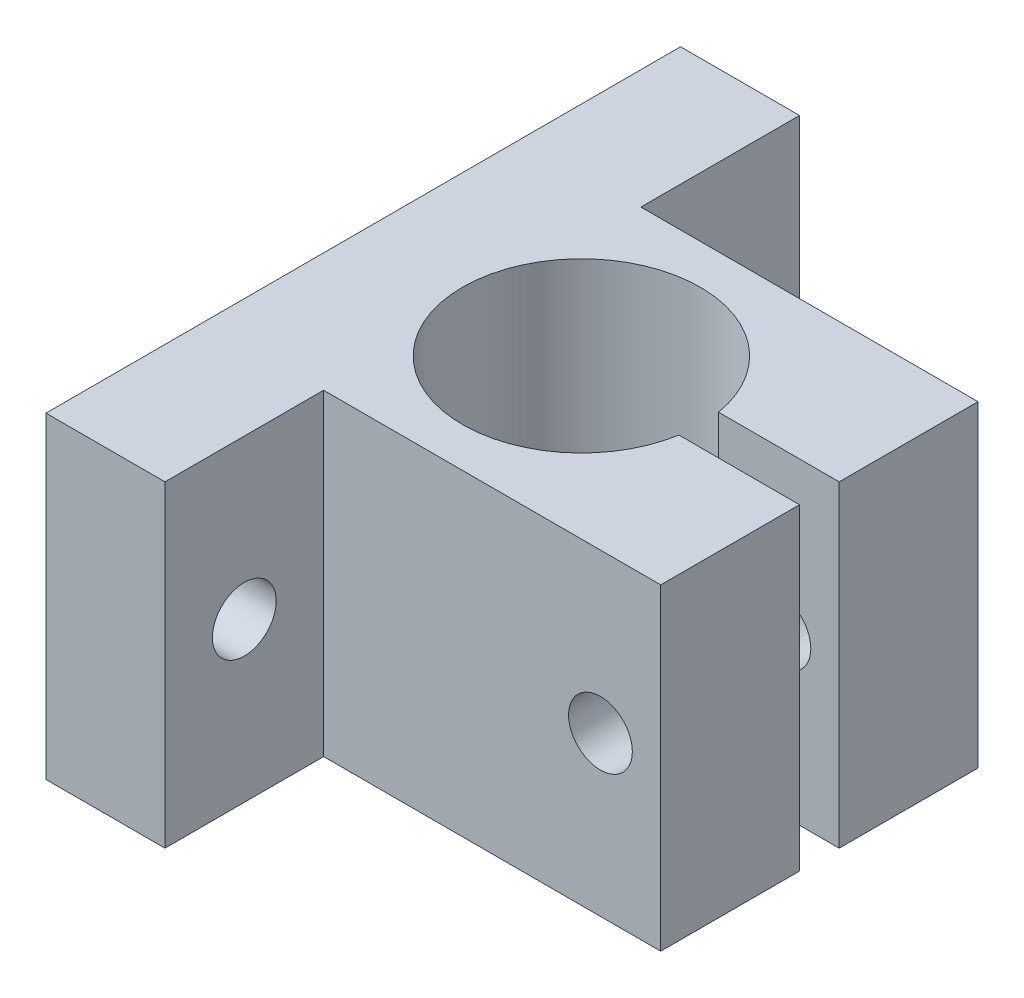
SolidWorks part; units mm, degrees
material "6061 Alloy"
ref_plane "Front Plane" through (0, 0, 0) normal (0, 0, 1) x (1, 0, 0)
ref_plane "Top Plane" through (0, 0, 0) normal (0, 1, 0) x (1, 0, 0)
ref_plane "Right Plane" through (0, 0, 0) normal (1, 0, 0) x (0, 0, -1)
sketch "Sketch1" plane through (0, 0, 0) normal (0, 1, 0) x (1, 0, 0)
  line L1 (-25.4, 25.4) -> (25.4, 25.4)
  line L2 (-25.4, 25.4) -> (-25.4, -25.4)
  line L3 (-25.4, -25.4) -> (25.4, -25.4)
  line L4 (25.4, 25.4) -> (25.4, -25.4)
  line L5 (-25.4, 25.4) -> (25.4, -25.4) construction
  line L6 (-25.4, -25.4) -> (25.4, 25.4) construction
  point P0 (0, 0)
  dimension "D1" = 50.8
  dimension "D2" = 50.8
extrude "Boss-Extrude1" add sketch "Sketch1" along normal mid plane 25.4
sketch "Sketch2" plane through (0, 12.7, 0) normal (0, 1, 0) x (1, 0, 0)
  line L0 (-25.4, 25.4) -> (-25.4, -25.4) construction
  circle A0 centre (-7.9375, 0) radius 9.525
  dimension "D1" = 19.05
  dimension "D2" = 17.4625
extrude "Cut-Extrude1" cut sketch "Sketch2" against normal through all
sketch "Sketch11" plane through (0, 12.7, 0) normal (0, 1, 0) x (1, 0, 0)
  line L0 (25.4, 25.4) -> (-25.4, 25.4) construction
  line L1 (11.1125, 25.4) -> (25.4, 25.4)
  line L2 (11.1125, 25.4) -> (11.1125, -25.4)
  line L3 (11.1125, -25.4) -> (25.4, -25.4)
  line L4 (25.4, 25.4) -> (25.4, -25.4)
  dimension "D1" = 14.2875
extrude "Cut-Extrude4" cut sketch "Sketch11" against normal through all
sketch "Sketch3" plane through (0, 12.7, 0) normal (0, 1, 0) x (1, 0, 0)
  line L0 (-25.4, -25.4) -> (11.1125, -25.4) construction
  line L1 (11.1125, 25.4) -> (-15.875, 25.4)
  line L2 (11.1125, 25.4) -> (11.1125, 12.7)
  line L3 (11.1125, 12.7) -> (-15.875, 12.7)
  line L4 (-15.875, 25.4) -> (-15.875, 12.7)
  line L5 (-15.875, -25.4) -> (11.1125, -25.4)
  line L6 (-15.875, -25.4) -> (-15.875, -12.7)
  line L7 (-15.875, -12.7) -> (11.1125, -12.7)
  line L8 (11.1125, -25.4) -> (11.1125, -12.7)
  line L10 (-25.4, 25.4) -> (-25.4, -25.4) construction
  line L11 (11.1125, 25.4) -> (11.1125, -25.4) construction
  line L12 (11.1125, 25.4) -> (-25.4, 25.4) construction
  dimension "D1" = 9.525
  dimension "D2" = 12.7
extrude "Cut-Extrude2" cut sketch "Sketch3" against normal through all
hole_wizard "#10 Clearance Hole1" positions "Sketch5" profile "Sketch4" hole size "#10" standard "ANSI Inch" end condition up to next
sketch "Sketch5" plane through (-15.875, 0, 0) normal (1, 0, 0) x (0, 0, -1)
  line L22 (-19.05, 12.7) -> (-19.05, -12.7) construction
  line L26 (19.05, 12.7) -> (19.05, -12.7) construction
  line L30 (-25.4, -12.7) -> (-25.4, 12.7) construction
  line L31 (-12.7, 12.7) -> (-25.4, 12.7) construction
  line L32 (-12.7, -12.7) -> (-25.4, -12.7) construction
  line L33 (25.4, -12.7) -> (12.7, -12.7) construction
  line L34 (25.4, 12.7) -> (12.7, 12.7) construction
  line L35 (25.4, -12.7) -> (25.4, 12.7) construction
  point P303 (-19.05, 0)
  point P558 (19.05, 0)
  dimension "D1" = 6.35
  dimension "D2" = 6.35
sketch "Sketch4" plane through (-15.875, 0, 19.05) normal (0, 1, 0) x (0, 0, -1)
  line L0 (0, 0) -> (0, 9.525)
  line L1 (0, 9.525) -> (2.5527, 9.525)
  line L2 (2.5527, 9.525) -> (2.5527, 0)
  line L5 (2.5527, 0) -> (0, 0)
  line L11 (0, -6.35) -> (0, 107.95) construction
  dimension "Thru Hole Dia." = 5.1054
  dimension "Thru Hole Depth" = 9.525
sketch "Sketch6" plane through (11.1125, 0, 0) normal (1, 0, 0) x (0, 0, -1)
  line L1 (0, 18.545) -> (0, -18.545) construction
  line L2 (-1.5875, 18.545) -> (1.5875, 18.545)
  line L3 (-1.5875, 18.545) -> (-1.5875, -18.545)
  line L4 (-1.5875, -18.545) -> (1.5875, -18.545)
  line L6 (1.5875, 18.545) -> (1.5875, -18.545)
  dimension "D1" = 3.175
extrude "Cut-Extrude3" cut sketch "Sketch6" against normal blind 24.13
hole_wizard "#10 Clearance Hole2" positions "Sketch8" profile "Sketch9" hole size "#10" standard "ANSI Inch" end condition through all
sketch "Sketch8" plane through (0, 0, 12.7) normal (0, 0, 1) x (1, 0, 0)
  line L0 (6.2865, 12.7) -> (6.2865, -12.7) construction
  line L1 (11.1125, 12.7) -> (-15.875, 12.7) construction
  line L2 (11.1125, -12.7) -> (-15.875, -12.7) construction
  line L4 (11.1125, -12.7) -> (11.1125, 12.7) construction
  point P13 (6.2865, 0)
  dimension "D3" = 4.826
sketch "Sketch9" plane through (6.2865, 0, 12.7) normal (1, 0, 0) x (0, -1, 0)
  line L0 (0, 0) -> (0, 38.1)
  line L1 (0, 38.1) -> (2.5527, 38.1)
  line L2 (2.5527, 38.1) -> (2.5527, 0)
  line L5 (2.5527, 0) -> (0, 0)
  line L11 (0, -6.35) -> (0, 107.95) construction
  dimension "Thru Hole Dia." = 5.1054
  dimension "Thru Hole Depth" = 38.1
sketch "Sketch10" plane through (-15.875, 0, 0) normal (1, 0, 0) x (0, 0, -1)
  circle A0 centre (19.05, 0) radius 4.7625 construction
  dimension "D1" = 9.525
fillet "Fillet1" [suppressed] radius 3.175
chamfer "Chamfer1" [suppressed] distance 0.508 angle 45
